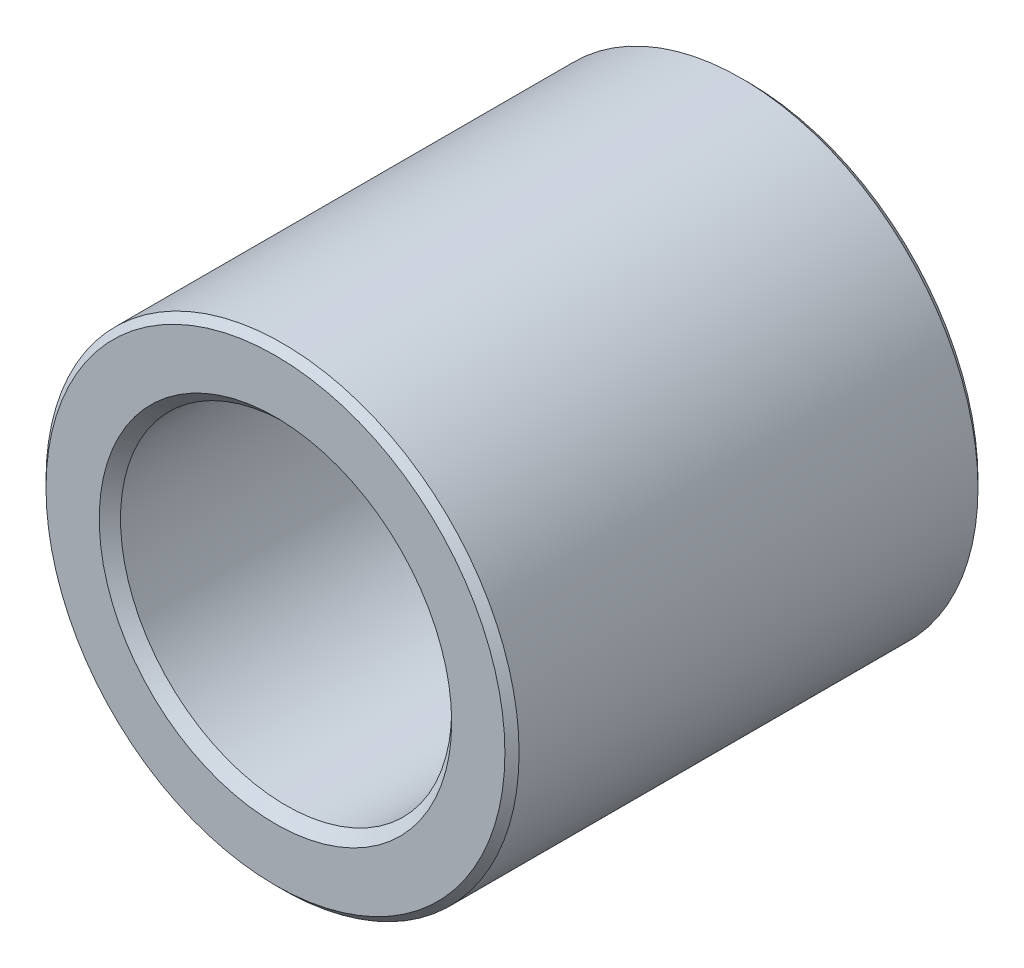
SolidWorks part; units mm, degrees
ref_plane "Front Plane" through (0, 0, 0) normal (0, 0, 1) x (1, 0, 0)
ref_plane "Top Plane" through (0, 0, 0) normal (0, 1, 0) x (1, 0, 0)
ref_plane "Right Plane" through (0, 0, 0) normal (1, 0, 0) x (0, 0, -1)
sketch "Sketch1" plane through (0, 0, 0) normal (0, 0, 1) x (1, 0, 0)
  circle A0 centre (0, 0) radius 3 construction
  circle A1 centre (0, 0) radius 2.1 construction
  point P4 (0, 3)
  dimension "ID" = 4.2
  dimension "OD" = 6
sketch "Sketch2" plane through (0, 0, 0) normal (1, 0, 0) x (0, 0, -1)
  line L0 (-3, 3) -> (3, 3) construction
  dimension "Length" = 6
sketch "Sketch3" plane through (0, 0, 0) normal (0, 0, 1) x (1, 0, 0)
  circle A0 centre (0, 0) radius 2.1 construction
  circle A1 centre (0, 0) radius 3 construction
  circle A2 centre (0, 0) radius 2.1
  circle A3 centre (0, 0) radius 3
extrude "Boss-Extrude1" add sketch "Sketch3" against normal up to vertex (3 mm away) and the other way up to vertex (3 mm away) up to point (0, 3, -3) other way up to point (0, 3, 3)
chamfer "Chamfer1" distance 0.09 angle 45 2 edges at (3, 0, 3) (3, 0, -3)
chamfer "Chamfer2" distance 0.135 angle 45 2 edges at (2.1, 0, 3) (2.1, 0, -3)
equation "\"D1@Chamfer1\"=(\"OD@Sketch1\"-\"ID@Sketch1\")*0.05"
equation "\"D1@Chamfer2\"=(\"OD@Sketch1\"-\"ID@Sketch1\")*0.075"
